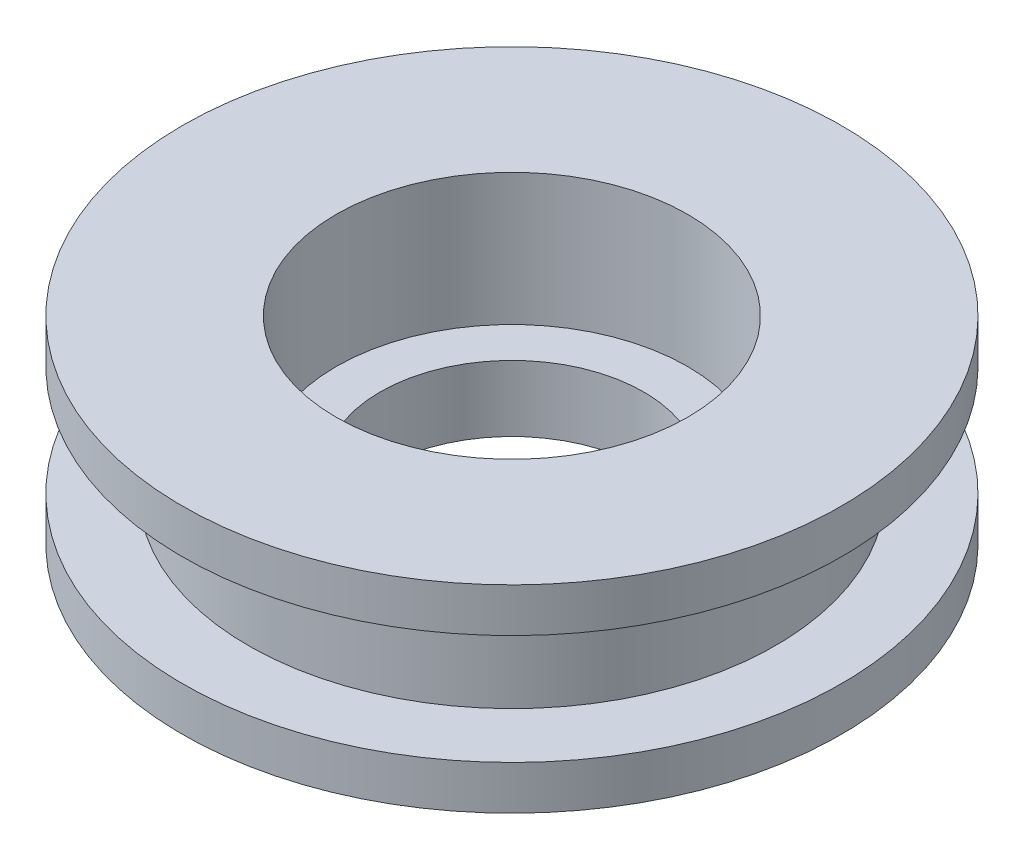
SolidWorks part; units mm, degrees
ref_plane "Plan de face" through (0, 0, 0) normal (0, 0, 1) x (1, 0, 0)
ref_plane "Plan de dessus" through (0, 0, 0) normal (0, 1, 0) x (1, 0, 0)
ref_plane "Plan de droite" through (0, 0, 0) normal (1, 0, 0) x (0, 0, -1)
sketch "Sketch1" plane through (0, 0, 0) normal (0, 0, 1) x (1, 0, 0)
  line L0 (0, 6.6206) -> (0, -3.6319) construction
  line L8 (4, 2.25) -> (4, -0.75)
  line L9 (4, 2.25) -> (7.5, 2.25)
  line L10 (7.5, 2.25) -> (7.5, 1.25)
  line L11 (7.5, 1.25) -> (6, 1.25)
  line L12 (6, 1.25) -> (6, -1.25)
  line L13 (6, -1.25) -> (7.5, -1.25)
  line L14 (7.5, -1.25) -> (7.5, -2.25)
  line L15 (7.5, -2.25) -> (3, -2.25)
  line L17 (3, -2.25) -> (3, -0.75)
  line L18 (3, -0.75) -> (4, -0.75)
  point P4 (6, 0)
  point P5 (3.6952, 2.25)
  dimension "D2" = 2
  dimension "D3" = 1.5
  dimension "D5" = 2.5
  dimension "D1" = 4
  dimension "D4" = 3
  dimension "D6" = 3
  dimension "D7" = 1
revolve "Revolve1" add sketch "Sketch1" angle 360 about L0
